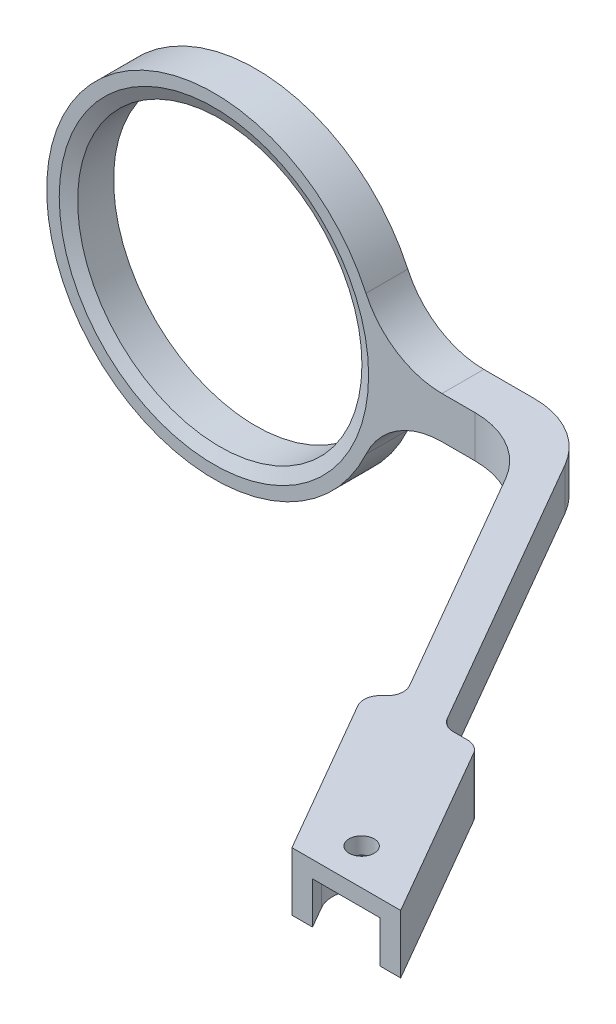
SolidWorks part; units mm, degrees
ref_plane "Plan de face" through (0, 0, 0) normal (0, 0, 1) x (1, 0, 0)
ref_plane "Plan de dessus" through (0, 0, 0) normal (0, 1, 0) x (1, 0, 0)
ref_plane "Plan de droite" through (0, 0, 0) normal (1, 0, 0) x (0, 0, -1)
sketch "Sketch1" plane through (0, 0, 0) normal (0, 0, 1) x (1, 0, 0)
  line L1 (0, 2.5) -> (37, 2.5)
  line L2 (0, 2.5) -> (0, -2.5)
  line L3 (0, -2.5) -> (37, -2.5)
  line L4 (37, 2.5) -> (37, -2.5)
  circle A0 centre (0, 0) radius 20
  circle A1 centre (0, 0) radius 17
  point P9 (0, 0)
  dimension "D1" = 40
  dimension "D3" = 37
  dimension "D4" = 5
  dimension "D2" = 3
extrude "Boss-Extrude1" add sketch "Sketch1" along normal blind 5 contours A1 L1 A0 L3 | A1 L3 A0 L1 | A0 L3 L4 L1 region at (-17.5646, 0, 0) region at (18.443, 0, 0) region at (28.4738, 0, 0)
chamfer "Chamfer2" distance 1.5 angle 25 1 edges at (17, 0, 5) first distance on face at (18.4608, 0, 5)
fillet "Fillet1" radius 10 2 edges at (19.8431, -2.5, 2.5) (19.8431, 2.5, 2.5)
sketch "Sketch4" plane through (0, 0, 0) normal (0, 1, 0) x (1, 0, 0)
  line L0 (18.5, -5) -> (17, -4.3005) construction
  circle A0 centre (0.2012, -29.5685) radius 30 construction
  dimension "D1" = 60
sketch "Sketch3" plane through (0, 2.5, 0) normal (0, 1, 0) x (1, 0, 0)
  line L0 (39.1132, 0) -> (74.3316, -61)
  line L1 (74.3316, -61) -> (69.3316, -61)
  line L2 (69.3316, -61) -> (37, -5)
  line L3 (27.2718, -5) -> (37, -5) construction
  line L4 (37, 0) -> (39.1132, 0)
  line L5 (37, -5) -> (37, 0)
  dimension "D1" = 120
  dimension "D2" = 61
  dimension "D3" = 5
extrude "Boss-Extrude2" add sketch "Sketch3" against normal up to surface (5 mm away) up to face at (32.1359, -2.5, 2.5)
sketch "Sketch5" plane through (0, 2.5, 0) normal (0, 1, 0) x (1, 0, 0)
  line L0 (65.3316, -61) -> (78.3316, -61)
  line L1 (69.3316, -61) -> (74.3316, -61) construction
  line L2 (65.3316, -61) -> (52.8316, -39.3494)
  line L3 (52.8316, -39.3494) -> (65.8316, -39.3494)
  line L4 (65.8316, -39.3494) -> (78.3316, -61)
  line L5 (37, -5) -> (69.3316, -61) construction
  point P4 (71.8316, -61)
  point P5 (71.8316, -61)
  dimension "D1" = 13
  dimension "D2" = 25
extrude "Boss-Extrude3" add sketch "Sketch5" against normal blind 7
sketch "Sketch9" plane through (0, -4.5, 0) normal (0, -1, 0) x (1, 0, 0)
  line L0 (71.8316, 61) -> (69.3316, 56.6699) construction
  line L1 (78.3316, 61) -> (65.3316, 61) construction
  line L2 (65.3316, 61) -> (52.8316, 39.3494) construction
  line L3 (66.3005, 58.4199) -> (67.7902, 61)
  line L4 (72.3627, 54.9199) -> (75.8731, 61)
  line L5 (67.7902, 61) -> (75.8731, 61)
  circle A0 centre (69.3316, 56.6699) radius 3.5
  dimension "D1" = 7
  dimension "D2" = 5
extrude "Cut-Extrude1" cut sketch "Sketch9" against normal blind 5 contours A0 | L0 L5 L3 A0 | L0 A0 L4 region at (73.3659, -4.5, 59.3501) region at (69.3501, -4.5, 60.4241) region at (72.277, -4.5, 58.3704)
sketch "Sketch10" plane through (0, 0.5, 0) normal (0, -1, 0) x (1, 0, 0)
  line L0 (67.1666, 57.9199) -> (71.4967, 55.4199)
  line L1 (67.1666, 57.9199) -> (59.1666, 44.0635)
  line L2 (59.1666, 44.0635) -> (63.4967, 41.5635)
  line L3 (63.4967, 41.5635) -> (71.4967, 55.4199)
  line L4 (52.8316, 39.3494) -> (65.3316, 61) construction
  point P2 (69.3316, 56.6699)
  point P3 (69.3316, 56.6699)
  dimension "D1" = 16
  dimension "D2" = 5
extrude "Cut-Extrude2" cut sketch "Sketch10" along normal blind 1.5
sketch "Sketch11" plane through (0, 2.5, 0) normal (0, 1, 0) x (1, 0, 0)
  circle A0 centre (69.3316, -56.6699) radius 1.5
  dimension "D1" = 3
extrude "Cut-Extrude3" cut sketch "Sketch11" against normal through all
fillet "Fillet2" radius 10 2 edges at (39.1132, 0, 0) (37, 0, 5)
fillet "Fillet3" radius 2 2 edges at (52.8316, -1, 39.3494) (65.8316, -1, 39.3494)
fillet "Fillet4" radius 2 2 edges at (61.8316, 0, 39.3494) (56.8316, 0, 39.3494)
